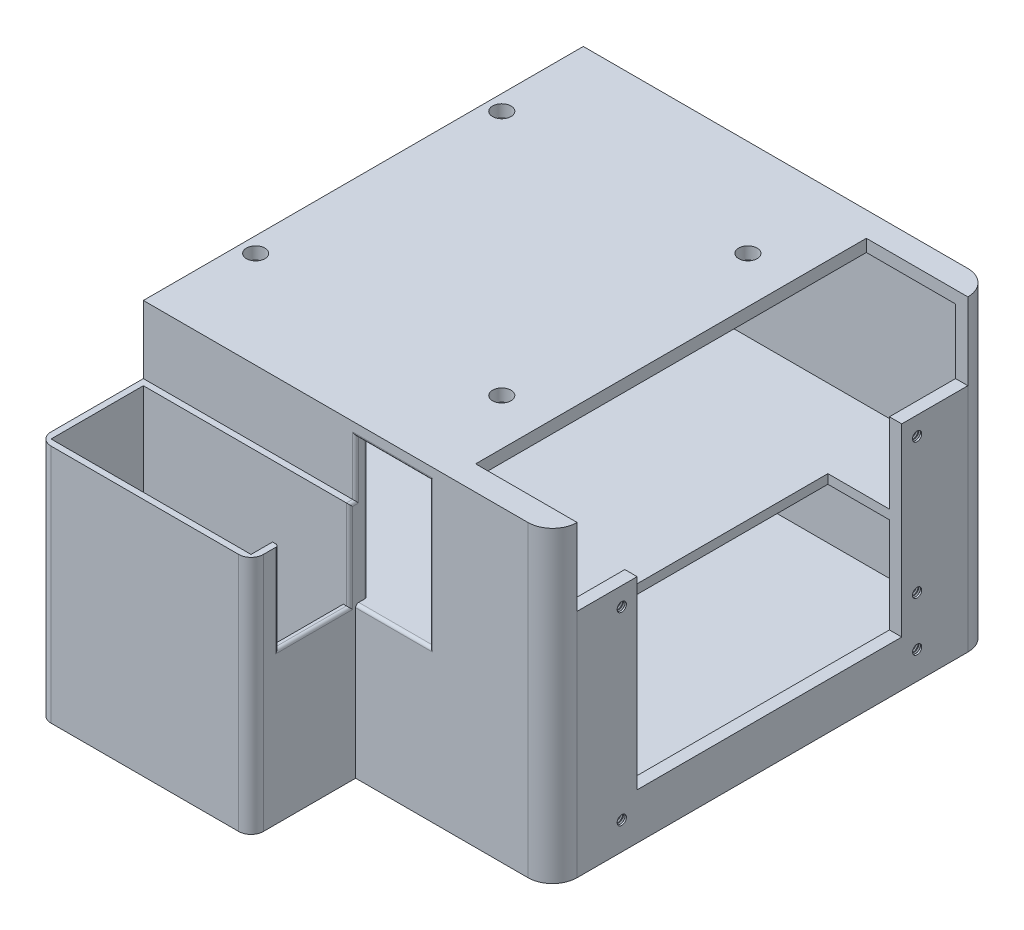
SolidWorks part; units mm, degrees
ref_plane "前视基准面" through (0, 0, 0) normal (0, 0, 1) x (1, 0, 0)
ref_plane "上视基准面" through (0, 0, 0) normal (0, 1, 0) x (1, 0, 0)
ref_plane "右视基准面" through (0, 0, 0) normal (1, 0, 0) x (0, 0, -1)
other "Configuration Table"
sketch "草图1" plane through (0, 0, 0) normal (0, 1, 0) x (1, 0, 0)
  line L1 (0, 0) -> (133, 0)
  line L2 (0, 0) -> (0, 143)
  line L3 (0, 143) -> (133, 143)
  line L4 (133, 0) -> (133, 143)
  dimension "D1" = 133
  dimension "D2" = 143
extrude "凸台-拉伸1" add sketch "草图1" along normal blind 100
sketch "草图3" plane through (0, 0, 0) normal (-1, 0, 0) x (0, 0, 1)
  line L1 (-139, 4) -> (-4, 4)
  line L2 (-139, 4) -> (-139, 46)
  line L3 (-139, 46) -> (-4, 46)
  line L4 (-4, 4) -> (-4, 46)
  line L5 (-143, 100) -> (-143, 0) construction
  line L6 (-143, 0) -> (0, 0) construction
  dimension "D1" = 135
  dimension "D2" = 42
  dimension "D3" = 4
  dimension "D4" = 4
extrude "切除-拉伸1" cut sketch "草图3" against normal offset from surface (129 mm away) 4 up to face at (133, 50, -71.5)
fillet "圆角1" radius 4 2 edges at (64.5, 46, -4) (64.5, 46, -139)
sketch "草图4" plane through (0, 0, 0) normal (-1, 0, 0) x (0, 0, 1)
  line L0 (-143, 100) -> (-143, 0) construction
  line L1 (-139, 96) -> (-4, 96)
  line L2 (-139, 96) -> (-139, 49)
  line L3 (-139, 49) -> (-4, 49)
  line L4 (-4, 96) -> (-4, 49)
  line L5 (-8, 46) -> (-135, 46) construction
  dimension "D1" = 135
  dimension "D2" = 4
  dimension "D3" = 47
  dimension "D4" = 3
extrude "切除-拉伸2" cut sketch "草图4" against normal offset from surface (129 mm away) 4 up to face at (133, 50, -71.5)
fillet "圆角2" radius 8 2 edges at (133, 50, 0) (133, 50, -143)
sketch "草图5" plane through (133, 0, 0) normal (1, 0, 0) x (0, 0, -1)
  circle A3 centre (118.5, 9) radius 1.5
  circle A4 centre (118.5, 25) radius 1.5
  circle A5 centre (118.5, 69) radius 1.5
  circle A6 centre (22.5, 69) radius 1.5
  circle A7 centre (22.5, 9) radius 1.5
extrude "切除-拉伸3" cut sketch "草图5" against normal through all
sketch "草图6" plane through (133, 0, 0) normal (1, 0, 0) x (0, 0, -1)
  line L0 (8, 100) -> (8, 75)
  line L1 (8, 100) -> (8, 0) construction
  line L2 (8, 75) -> (27.5, 75)
  line L3 (27.5, 75) -> (27.5, 15)
  line L4 (27.5, 15) -> (113.5, 15)
  line L5 (110.5, 15) -> (30.5, 15) construction
  line L6 (113.5, 15) -> (113.5, 75)
  line L7 (113.5, 75) -> (135, 75)
  line L8 (135, 0) -> (135, 100) construction
  line L10 (135, 75) -> (135, 100)
  line L11 (135, 100) -> (8, 100)
extrude "切除-拉伸4" cut sketch "草图6" against normal blind 4
sketch "草图7" plane through (0, 100, 0) normal (0, 1, 0) x (1, 0, 0)
  line L1 (125, 143) -> (0, 143) construction
  line L3 (0, 143) -> (0, 0) construction
  circle A0 centre (5, 111.5) radius 3
  circle A1 centre (85, 111.5) radius 3
  circle A2 centre (85, 31.5) radius 3
  circle A3 centre (5, 31.5) radius 3
  dimension "D1" = 6
  dimension "D2" = 6
  dimension "D3" = 6
  dimension "D4" = 6
  dimension "D5" = 80
  dimension "D6" = 31.5
  dimension "D7" = 80
  dimension "D8" = 5
  dimension "D9" = 80
extrude "切除-拉伸5" cut sketch "草图7" against normal up to next
sketch "草图8" plane through (0, 0, 0) normal (0, -1, 0) x (1, 0, 0)
  line L0 (0, 0) -> (69, 0)
  line L1 (0, 0) -> (125, 0) construction
  line L2 (69, 0) -> (69, 4)
  line L4 (0, 2) -> (0, 0)
  line L5 (0, 2) -> (0, 34)
  line L7 (69, 34) -> (69, 4)
  line L8 (69, 34) -> (0, 34)
  dimension "D1" = 34
  dimension "D3" = 69
extrude "凸台-拉伸2" add sketch "草图8" against normal blind 78
sketch "草图9" plane through (0, 78, 0) normal (0, 1, 0) x (1, 0, 0)
  line L0 (0, -34) -> (0, 0) construction
  line L1 (1.9975, -2) -> (66.9975, -2)
  line L2 (1.9975, -2) -> (1.9975, -32)
  line L3 (1.9975, -32) -> (66.9975, -32)
  line L4 (66.9975, -2) -> (66.9975, -32)
  line L5 (0, 0) -> (125, 0) construction
  dimension "D1" = 65
  dimension "D2" = 1.9975
  dimension "D3" = 2
  dimension "D4" = 30
extrude "切除-拉伸6" cut sketch "草图9" against normal offset from surface (76 mm away) 2 up to face at (82.1642, 0, -45.125)
sketch "草图10" plane through (69, 0, 0) normal (1, 0, 0) x (0, 0, -1)
  line L1 (-25, 78) -> (-2, 78)
  line L2 (-25, 78) -> (-25, 49)
  line L3 (-25, 49) -> (-2, 49)
  line L4 (-2, 78) -> (-2, 49)
  line L5 (0, 78) -> (0, 0) construction
  line L6 (0, 78) -> (-34, 78) construction
  dimension "D1" = 29
  dimension "D2" = 23
  dimension "D3" = 2
extrude "切除-拉伸7" cut sketch "草图10" against normal up to next
sketch "草图11" plane through (0, 0, 0) normal (0, 0, 1) x (1, 0, 0)
  line L0 (69, 78) -> (69, 0) construction
  line L1 (69, 49) -> (93, 49)
  line L2 (69, 49) -> (69, 96)
  line L3 (69, 96) -> (93, 96)
  line L4 (93, 49) -> (93, 96)
  line L5 (0, 100) -> (125, 100) construction
  dimension "D1" = 24
  dimension "D2" = 47
  dimension "D3" = 4
extrude "切除-拉伸8" cut sketch "草图11" against normal up to next
fillet "圆角3" radius 4 2 edges at (0, 39, 34) (69, 39, 34)
fillet "圆角4" radius 1 10 edges at (69, 78, 1) (81, 96, 0) (93, 72.5, -4) (93, 72.5, 0) (69, 87, 0) (69, 72.5, -4) (81, 49, 0) (69, 63.5, 2) (69, 63.5, 25) (69, 49, 13.5)
sketch "草图12" plane through (129, 0, 0) normal (1, 0, 0) x (0, 0, -1)
  line L4 (8, 96) -> (135, 96)
  line L5 (135, 96) -> (135, 100)
  line L6 (135, 100) -> (8, 100)
  line L7 (8, 100) -> (8, 96)
  line L8 (8, 96) -> (135, 96)
  line L9 (135, 96) -> (135, 100)
  line L10 (135, 100) -> (8, 100)
  line L11 (8, 100) -> (8, 96)
  dimension "D1" = 0
extrude "切除-拉伸9" cut sketch "草图12" against normal blind 29
sketch "草图13" plane through (129, 0, 0) normal (1, 0, 0) x (0, 0, -1)
  line L4 (27.5, 46) -> (113.5, 46)
  line L5 (113.5, 46) -> (113.5, 49)
  line L6 (113.5, 49) -> (27.5, 49)
  line L7 (27.5, 49) -> (27.5, 46)
  line L8 (27.5, 46) -> (113.5, 46)
  line L9 (113.5, 46) -> (113.5, 49)
  line L10 (113.5, 49) -> (27.5, 49)
  line L11 (27.5, 49) -> (27.5, 46)
  dimension "D1" = 0
extrude "切除-拉伸10" cut sketch "草图13" against normal blind 20
thread "螺纹线1" pitch 0.8 method cut profile "螺纹线轮廓1" start angle 0, offset 0, length 0, pitch 0.8, diameter 3
ref_plane "基准面1" through (133, 9, -117) normal (0, -1, 0) x (0, 0, 1)
sketch "螺纹线轮廓1" plane through (133, 9, -117) normal (0, -1, 0) x (0, 0, 1)
  line L0 (0, 0) -> (0, 0.8) construction
  line L1 (0, 0) -> (0.433, 0.25)
  line L2 (0.433, 0.25) -> (0.433, 0.35)
  line L3 (0.433, 0.35) -> (0, 0.6)
  line L4 (0.433, 0.3) -> (0, 0.3) construction
  line L11 (0, 0) -> (0, 0.6)
  point P2 (0, 0)
  dimension "Pitch" = 0.8
  dimension "Profile_Angle" = 60
  dimension "Profile_Land" = 0.1
  dimension "Profile_Height" = 0.433
thread "螺纹线2" pitch 0.8 method cut profile "螺纹线轮廓2" start angle 0, offset 0, length 0, pitch 0.8, diameter 3
ref_plane "基准面2" through (133, 25, -117) normal (0, -1, 0) x (0, 0, 1)
sketch "螺纹线轮廓2" plane through (133, 25, -117) normal (0, -1, 0) x (0, 0, 1)
  line L0 (0, 0) -> (0, 0.8) construction
  line L1 (0, 0) -> (0.433, 0.25)
  line L2 (0.433, 0.25) -> (0.433, 0.35)
  line L3 (0.433, 0.35) -> (0, 0.6)
  line L4 (0.433, 0.3) -> (0, 0.3) construction
  line L11 (0, 0) -> (0, 0.6)
  point P2 (0, 0)
  dimension "Pitch" = 0.8
  dimension "Profile_Angle" = 60
  dimension "Profile_Land" = 0.1
  dimension "Profile_Height" = 0.433
thread "螺纹线3" pitch 0.8 method cut profile "螺纹线轮廓3" start angle 0, offset 0, length 0, pitch 0.8, diameter 3
ref_plane "基准面3" through (133, 69, -117) normal (0, -1, 0) x (0, 0, 1)
sketch "螺纹线轮廓3" plane through (133, 69, -117) normal (0, -1, 0) x (0, 0, 1)
  line L0 (0, 0) -> (0, 0.8) construction
  line L1 (0, 0) -> (0.433, 0.25)
  line L2 (0.433, 0.25) -> (0.433, 0.35)
  line L3 (0.433, 0.35) -> (0, 0.6)
  line L4 (0.433, 0.3) -> (0, 0.3) construction
  line L11 (0, 0) -> (0, 0.6)
  point P2 (0, 0)
  dimension "Pitch" = 0.8
  dimension "Profile_Angle" = 60
  dimension "Profile_Land" = 0.1
  dimension "Profile_Height" = 0.433
thread "螺纹线4" pitch 0.8 method cut profile "螺纹线轮廓4" start angle 0, offset 0, length 0, pitch 0.8, diameter 3
ref_plane "基准面4" through (133, 69, -21) normal (0, -1, 0) x (0, 0, 1)
sketch "螺纹线轮廓4" plane through (133, 69, -21) normal (0, -1, 0) x (0, 0, 1)
  line L0 (0, 0) -> (0, 0.8) construction
  line L1 (0, 0) -> (0.433, 0.25)
  line L2 (0.433, 0.25) -> (0.433, 0.35)
  line L3 (0.433, 0.35) -> (0, 0.6)
  line L4 (0.433, 0.3) -> (0, 0.3) construction
  line L11 (0, 0) -> (0, 0.6)
  point P2 (0, 0)
  dimension "Pitch" = 0.8
  dimension "Profile_Angle" = 60
  dimension "Profile_Land" = 0.1
  dimension "Profile_Height" = 0.433
thread "螺纹线5" pitch 0.8 method cut profile "螺纹线轮廓5" start angle 0, offset 0, length 0, pitch 0.8, diameter 3
ref_plane "基准面5" through (133, 9, -21) normal (0, -1, 0) x (0, 0, 1)
sketch "螺纹线轮廓5" plane through (133, 9, -21) normal (0, -1, 0) x (0, 0, 1)
  line L0 (0, 0) -> (0, 0.8) construction
  line L1 (0, 0) -> (0.433, 0.25)
  line L2 (0.433, 0.25) -> (0.433, 0.35)
  line L3 (0.433, 0.35) -> (0, 0.6)
  line L4 (0.433, 0.3) -> (0, 0.3) construction
  line L11 (0, 0) -> (0, 0.6)
  point P2 (0, 0)
  dimension "Pitch" = 0.8
  dimension "Profile_Angle" = 60
  dimension "Profile_Land" = 0.1
  dimension "Profile_Height" = 0.433
